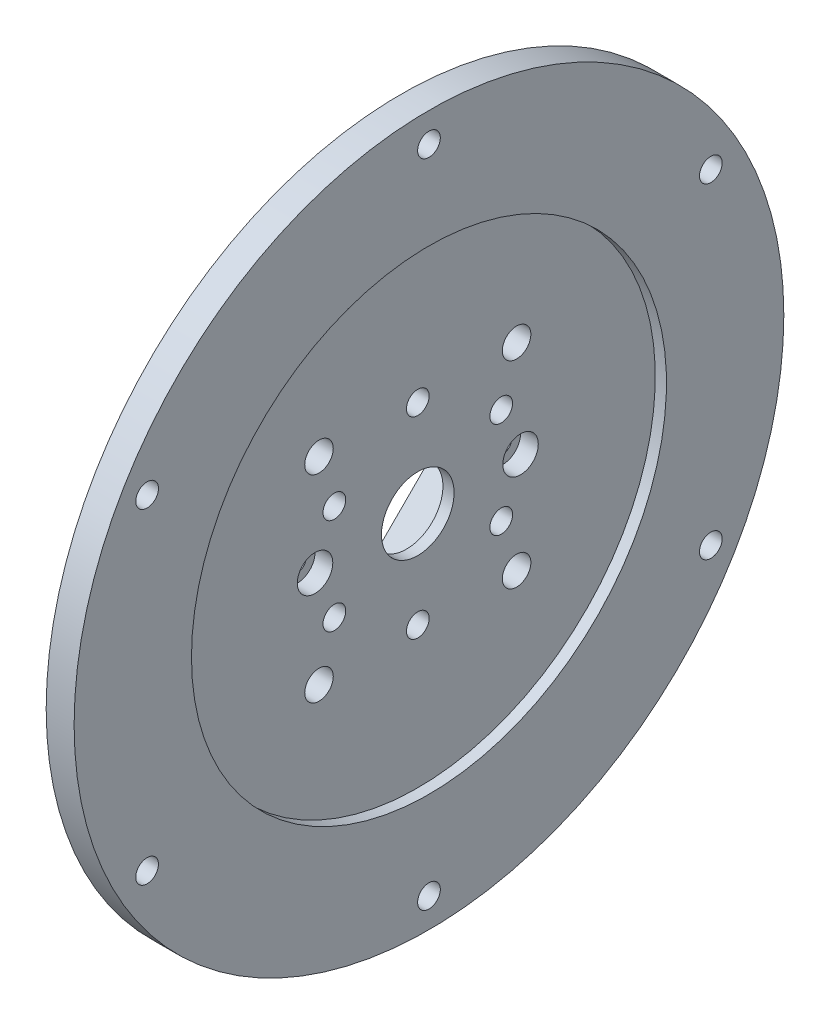
SolidWorks part; units mm, degrees
ref_plane "Front Plane" through (0, 0, 0) normal (0, 0, 1) x (1, 0, 0)
ref_plane "Top Plane" through (0, 0, 0) normal (0, 1, 0) x (1, 0, 0)
ref_plane "Right Plane" through (0, 0, 0) normal (1, 0, 0) x (0, 0, -1)
sketch "Sketch1" plane through (0, 0, 0) normal (0, 0, 1) x (1, 0, 0)
  line L0 (0, 0) -> (58.591, 0) construction
  line L2 (0, 0) -> (18.4, 0)
  line L3 (0, 0) -> (0, 2.5)
  line L4 (0, 2.5) -> (18.4, 2.5)
  line L5 (18.4, 0) -> (18.4, 2.5)
  line L6 (6, 2.5) -> (6, 6)
  line L11 (6, 6) -> (9.97, 6)
  line L16 (12.97, 6) -> (12.97, 3)
  line L17 (12.97, 3) -> (13.6304, 3)
  line L18 (13.6304, 3) -> (13.6304, 2.5)
  line L19 (13.6304, 2.5) -> (6, 2.5)
  line L22 (13.6304, 2.5) -> (16.1104, 2.5)
  line L23 (13.6304, 2.5) -> (13.6304, 4)
  line L24 (13.6304, 4) -> (16.1104, 4)
  line L25 (16.1104, 2.5) -> (16.1104, 4)
  line L27 (6, 6) -> (9.97, 6)
  line L28 (6, 6) -> (6, 9)
  line L29 (6, 9) -> (9.97, 9)
  line L30 (9.97, 6) -> (9.97, 9)
  line L31 (6, 9) -> (6, 8.25)
  line L32 (6, 8.25) -> (5, 8.25)
  line L33 (8.58, 22.001) -> (8.58, 12.476) construction
  line L34 (5, 12.476) -> (12.16, 12.476)
  line L35 (9.97, 9) -> (12.16, 9)
  line L36 (5, 7.5) -> (3, 7.5)
  line L37 (5, 8.25) -> (5, 12.476)
  line L38 (5, 7.5) -> (5, 14)
  line L39 (5, 14) -> (3, 14)
  line L40 (3, 7.5) -> (3, 14)
  line L41 (5, 22.001) -> (12.16, 22.001)
  line L42 (5, 22.001) -> (5, 30.1625)
  line L43 (5, 30.1625) -> (12.16, 30.1625)
  line L44 (12.16, 22.001) -> (12.16, 30.1625)
  line L49 (16.6304, 22.001) -> (16.6304, 7.5)
  line L51 (23.0104, 7.5) -> (23.0104, 6.5)
  line L54 (16.1104, 4) -> (13.6304, 4)
  line L56 (18.0304, 7.5) -> (23.0104, 7.5)
  line L57 (13.16, 22.001) -> (16.6304, 22.001)
  line L58 (16.1104, 3.5) -> (20.0104, 3.5)
  line L59 (29.9004, 14) -> (26.9004, 11)
  line L60 (4, 31.75) -> (18.0304, 31.75)
  line L61 (18.0304, 7.5) -> (23.0104, 7.5)
  line L62 (18.0304, 7.5) -> (18.0304, 12)
  line L63 (18.0304, 12) -> (23.0104, 12)
  line L64 (23.0104, 7.5) -> (23.0104, 12)
  line L65 (18.0304, 31.75) -> (18.0304, 12)
  line L66 (23.0104, 11) -> (26.9004, 11)
  line L67 (34.8004, 23) -> (31.3004, 19.5)
  line L68 (35.8004, 31) -> (38.7904, 33.99)
  line L69 (29.9004, 14) -> (29.9004, 15)
  line L70 (29.9004, 15) -> (22.9304, 15)
  line L71 (22.9304, 15) -> (21.0304, 15)
  line L72 (18.0304, 7.5) -> (16.6304, 7.5)
  line L73 (21.0304, 15) -> (21.0304, 43)
  line L74 (20.0304, 40) -> (10.0704, 40)
  line L75 (10.0704, 40) -> (4, 40)
  line L76 (21.0304, 43) -> (20.0304, 43)
  line L77 (22.9304, 15) -> (29.9004, 15)
  line L78 (22.9304, 15) -> (22.9304, 21)
  line L79 (22.9304, 21) -> (29.9004, 21)
  line L80 (29.9004, 15) -> (29.9004, 21)
  line L81 (10.0704, 40) -> (20.0304, 40)
  line L82 (10.0704, 40) -> (10.0704, 50)
  line L83 (10.0704, 50) -> (20.0304, 50)
  line L84 (20.0304, 40) -> (20.0304, 50)
  line L85 (4, 40) -> (4, 31.75)
  line L86 (12.97, 3) -> (12.97, 2.5)
  line L87 (31.3004, 19.5) -> (29.9004, 19.5)
  line L88 (21.51, 63.5) -> (21.51, 44)
  line L89 (21.51, 63.5) -> (25.9304, 63.5)
  line L90 (25.9304, 63.5) -> (25.9304, 25)
  line L91 (27.8304, 25) -> (25.9304, 25)
  line L92 (10.0704, 48) -> (9, 48)
  line L93 (9, 48) -> (9, 53.476)
  line L94 (9, 53.476) -> (20.0304, 53.476)
  line L95 (20.0304, 53.476) -> (20.0304, 50)
  line L96 (14.5152, 63.001) -> (14.5152, 53.476) construction
  line L97 (9, 63.001) -> (20.0304, 63.001)
  line L98 (9, 63.001) -> (9, 68.2625)
  line L99 (9, 68.2625) -> (20.0304, 68.2625)
  line L100 (20.0304, 63.001) -> (20.0304, 68.2625)
  line L101 (12.97, 6) -> (11.97, 6)
  line L102 (9, 42.5) -> (5, 42.5)
  line L103 (9, 42.5) -> (9, 55)
  line L104 (9, 55) -> (5, 55)
  line L105 (5, 42.5) -> (5, 55)
  line L106 (9.97, 6) -> (10.87, 6)
  line L107 (27.8304, 25) -> (34.8004, 25)
  line L108 (34.8004, 25) -> (34.8004, 23)
  line L109 (0, 0) -> (-2, 0)
  line L110 (0, 0) -> (0, 11)
  line L111 (27.8304, 25) -> (34.8004, 25)
  line L112 (27.8304, 25) -> (27.8304, 32.5)
  line L113 (27.8304, 32.5) -> (34.8004, 32.5)
  line L114 (34.8004, 25) -> (34.8004, 32.5)
  line L115 (35.8004, 31) -> (34.8004, 31)
  line L116 (27.8304, 32.5) -> (27.8304, 64.5)
  line L117 (21.1827, 74.025) -> (6.8477, 74.025)
  line L118 (6.8477, 74.025) -> (6.8477, 76.2)
  line L119 (38.7904, 47.29) -> (30.8304, 55.25)
  line L120 (0, 11) -> (-2, 11)
  line L121 (38.7904, 43.815) -> (30.8529, 43.815)
  line L123 (-4.8, 69.85) -> (1.55, 76.2)
  line L124 (38.7904, 47.29) -> (38.7904, 33.99)
  line L125 (-2, 0) -> (-2, 11)
  line L126 (38.7904, 37.465) -> (30.8529, 37.465)
  line L127 (30.8529, 43.815) -> (30.8529, 37.465)
  line L128 (6, 2.5) -> (6, 0)
  line L129 (0, 63.5) -> (0, 30)
  line L132 (5, 63.5) -> (0, 63.5)
  line L136 (-1.8, 30) -> (-11.76, 30)
  line L138 (-13.76, 25.4) -> (-2, 25.4)
  line L139 (-2, 25.4) -> (-2, 11.5)
  line L140 (27.8304, 64.5) -> (21.1827, 64.5)
  line L141 (-1.8, 30) -> (-11.76, 30)
  line L142 (-1.8, 30) -> (-1.8, 39)
  line L143 (-1.8, 39) -> (-11.76, 39)
  line L144 (-11.76, 30) -> (-11.76, 39)
  line L145 (21.1827, 64.5) -> (21.1827, 74.025)
  line L146 (-12.76, 37) -> (-12.76, 47.29)
  line L147 (-12.76, 37) -> (-11.76, 37)
  line L148 (30.8304, 55.25) -> (30.8304, 76.2)
  line L149 (11.97, 6) -> (11.97, 5.45)
  line L154 (-2, 11.5) -> (1, 11.5)
  line L155 (5, 60.6197) -> (24.05, 60.6197)
  line L160 (5, 60.6197) -> (5, 55.8572)
  line L161 (5, 55.8572) -> (24.05, 55.8572)
  line L166 (24.05, 60.6197) -> (24.05, 55.8572)
  line L167 (5, 60.6197) -> (24.05, 55.8572) construction
  line L172 (5, 55.8572) -> (24.05, 60.6197) construction
  line L173 (24.05, 62.2072) -> (25.9304, 62.2072)
  line L174 (11.97, 5.45) -> (10.87, 5.45)
  line L175 (10.87, 6) -> (10.87, 5.45)
  line L176 (24.05, 62.2072) -> (24.05, 54.2697)
  line L177 (24.05, 54.2697) -> (25.9304, 54.2697)
  line L178 (25.9304, 62.2072) -> (25.9304, 54.2697)
  line L179 (24.05, 62.2072) -> (25.9304, 54.2697) construction
  line L180 (24.05, 54.2697) -> (25.9304, 62.2072) construction
  line L181 (3, 19.6197) -> (15.7, 19.6197)
  line L182 (3, 19.6197) -> (3, 14.8572)
  line L183 (3, 14.8572) -> (15.7, 14.8572)
  line L184 (15.7, 19.6197) -> (15.7, 14.8572)
  line L185 (3, 19.6197) -> (15.7, 14.8572) construction
  line L186 (3, 14.8572) -> (15.7, 19.6197) construction
  line L187 (15.7, 21.2072) -> (16.6304, 21.2072)
  line L188 (15.7, 21.2072) -> (15.7, 13.2697)
  line L189 (15.7, 13.2697) -> (16.6304, 13.2697)
  line L190 (16.6304, 21.2072) -> (16.6304, 13.2697)
  line L191 (15.7, 21.2072) -> (16.6304, 13.2697) construction
  line L192 (15.7, 13.2697) -> (16.6304, 21.2072) construction
  line L193 (1, 11.5) -> (1, 6.5)
  line L194 (1, 6.5) -> (3, 6.5)
  line L195 (23.0104, 6.5) -> (20.0104, 3.5)
  line L196 (5, 63.5) -> (5, 42.5)
  line L197 (5, 42.5) -> (3, 42.5)
  line L198 (3, 42.5) -> (3, 6.5)
  line L199 (6, 0) -> (12.97, 0)
  line L200 (12.97, 0) -> (12.97, 2.5)
  line L201 (18.0304, 31.75) -> (18.0304, 35.875)
  line L202 (18.0304, 35.875) -> (21.0304, 35.875)
  line L203 (30.8304, 76.2) -> (6.8477, 76.2)
  line L204 (3.4027, 69.85) -> (7.8477, 69.85) construction
  line L205 (7.8477, 67.4687) -> (26.8977, 67.4688)
  line L206 (7.8477, 74.025) -> (7.8477, 64.5)
  line L207 (7.8477, 64.5) -> (-1.8, 64.5)
  line L208 (-1.8, 64.5) -> (-1.8, 39)
  line L209 (-12.76, 47.29) -> (-4.8, 55.25)
  line L210 (-4.8, 55.25) -> (-4.8, 69.85)
  line L211 (7.8477, 67.4687) -> (7.8477, 72.2313)
  line L212 (7.8477, 72.2313) -> (26.8977, 72.2313)
  line L213 (26.8977, 67.4688) -> (26.8977, 72.2313)
  line L214 (26.8977, 73.8187) -> (30.8304, 73.8187)
  line L215 (26.8977, 73.8187) -> (26.8977, 65.8813)
  line L216 (26.8977, 65.8813) -> (30.8304, 65.8813)
  line L217 (30.8304, 73.8187) -> (30.8304, 65.8813)
  line L218 (3.4027, 72.2313) -> (25.6277, 72.2313)
  line L219 (3.4027, 72.2313) -> (3.4027, 67.4687)
  line L220 (3.4027, 67.4687) -> (25.6277, 67.4687)
  line L221 (25.6277, 72.2313) -> (25.6277, 67.4687)
  line L222 (25.6277, 69.85) -> (21.1827, 69.85) construction
  line L223 (21.51, 44) -> (22.9304, 44)
  line L224 (22.9304, 44) -> (22.9304, 21)
  line L225 (13.6304, 4) -> (13.6304, 12.2697)
  line L226 (13.6304, 12.2697) -> (13.16, 12.2697)
  line L227 (13.16, 12.2697) -> (13.16, 22.001)
  line L228 (12.16, 9) -> (12.16, 12.476)
  line L229 (-1.8, 30) -> (0, 30)
  line L230 (9, 65.6317) -> (3.4027, 65.6317) construction
  line L231 (20.0304, 65.6317) -> (25.6277, 65.6317) construction
  line L232 (1.55, 76.2) -> (6.8477, 76.2)
  line L233 (-11.76, 30) -> (-13.76, 30)
  line L234 (-13.76, 30) -> (-13.76, 25.4)
  circle A0 centre (26.8804, 25.95) radius 0.95
  circle A1 centre (21.9804, 15.95) radius 0.95
  circle A2 centre (17.3304, 8.2) radius 0.7
  circle A3 centre (10.42, 6.45) radius 0.45
  circle A4 centre (-0.9, 30.9) radius 0.9
  point P7 (24.9902, 58.2385)
  point P131 (16.1652, 17.2385)
  point P135 (14.525, 58.2385)
  point P146 (9.35, 17.2385)
sketch "Sketch2" plane through (0, 0, 0) normal (0, 0, 1) x (1, 0, 0)
  line L0 (-1.8, 30) -> (-11.76, 30) construction
  line L1 (-2, 25.4) -> (-2, 11.5) construction
  line L3 (-13.76, 25.4) -> (-2, 25.4) construction
  line L4 (-2, 11.5) -> (1, 11.5) construction
  line L5 (1, 11.5) -> (1, 6.5) construction
  line L6 (1, 6.5) -> (3, 6.5) construction
  line L7 (3, 42.5) -> (3, 6.5) construction
  line L8 (5, 42.5) -> (3, 42.5) construction
  line L9 (5, 63.5) -> (5, 42.5) construction
  line L10 (5, 63.5) -> (0, 63.5) construction
  line L11 (0, 63.5) -> (0, 30) construction
  line L14 (-1.8, 30) -> (-11.76, 30)
  line L15 (-2, 25.4) -> (-2, 11.5)
  line L17 (-13.76, 25.4) -> (-2, 25.4)
  line L18 (-2, 11.5) -> (1, 11.5)
  line L19 (1, 11.5) -> (1, 6.5)
  line L20 (1, 6.5) -> (3, 6.5)
  line L21 (3, 42.5) -> (3, 6.5)
  line L22 (5, 42.5) -> (3, 42.5)
  line L23 (5, 63.5) -> (5, 42.5)
  line L24 (5, 63.5) -> (0, 63.5)
  line L25 (0, 63.5) -> (0, 30)
  line L28 (-1.8, 30) -> (0, 30) construction
  line L29 (-1.8, 30) -> (0, 30)
  line L30 (-13.76, 30) -> (-13.76, 25.4) construction
  line L31 (-11.76, 30) -> (-13.76, 30) construction
  line L32 (-13.76, 30) -> (-13.76, 25.4)
  line L33 (-11.76, 30) -> (-13.76, 30)
revolve "Revolve1" add sketch "Sketch2" angle 360 about L0 region at (-0.9, 29.3999, 0)
sketch "Sketch3" plane through (0, 0, 0) normal (1, 0, 0) x (0, 0, -1)
  line L0 (0, 0) -> (0, 69.85) construction
  line L1 (0, 0) -> (13.6271, 68.5079) construction
  line L2 (0, 0) -> (0, 58.2385) construction
  line L3 (0, 0) -> (50.436, 29.1192) construction
  line L4 (0, 0) -> (0, 31.75) construction
  line L5 (0, 0) -> (12.1502, 29.3332) construction
  line L6 (0, 0) -> (0, 17.2385) construction
  line L7 (0, 0) -> (14.929, 8.6192) construction
  line L8 (0, 0) -> (0, 58.2385) construction
  line L9 (0, 0) -> (50.436, 29.1192) construction
  line L10 (0, 0) -> (5.9583, 29.9542) construction
  line L11 (0, 0) -> (16.9677, 25.394) construction
  circle A0 centre (0, 0) radius 69.85 construction
  circle A1 centre (0, 0) radius 58.2385 construction
  circle A2 centre (0, 0) radius 31.75 construction
  circle A3 centre (0, 0) radius 17.2385 construction
  circle A4 centre (0, 69.85) radius 3.175
  circle A5 centre (0, 58.2385) radius 4.7625
  circle A6 centre (0, 31.75) radius 3.175
  circle A7 centre (0, 17.2385) radius 4.7625
  circle A8 centre (13.6271, 68.5079) radius 3.175
  circle A9 centre (26.7304, 64.533) radius 3.175
  circle A10 centre (38.8066, 58.0782) radius 3.175
  circle A11 centre (49.3914, 49.3914) radius 3.175
  circle A12 centre (58.0782, 38.8066) radius 3.175
  circle A13 centre (64.533, 26.7304) radius 3.175
  circle A14 centre (68.5079, 13.6271) radius 3.175
  circle A15 centre (69.85, 0) radius 3.175
  circle A16 centre (68.5079, -13.6271) radius 3.175
  circle A17 centre (64.533, -26.7304) radius 3.175
  circle A18 centre (58.0782, -38.8066) radius 3.175
  circle A19 centre (49.3914, -49.3914) radius 3.175
  circle A20 centre (38.8066, -58.0782) radius 3.175
  circle A21 centre (26.7304, -64.533) radius 3.175
  circle A22 centre (13.6271, -68.5079) radius 3.175
  circle A23 centre (0, -69.85) radius 3.175
  circle A24 centre (-13.6271, -68.5079) radius 3.175
  circle A25 centre (-26.7304, -64.533) radius 3.175
  circle A26 centre (-38.8066, -58.0782) radius 3.175
  circle A27 centre (-49.3914, -49.3914) radius 3.175
  circle A28 centre (-58.0782, -38.8066) radius 3.175
  circle A29 centre (-64.533, -26.7304) radius 3.175
  circle A30 centre (-68.5079, -13.6271) radius 3.175
  circle A31 centre (-69.85, 0) radius 3.175
  circle A32 centre (-68.5079, 13.6271) radius 3.175
  circle A33 centre (-64.533, 26.7304) radius 3.175
  circle A34 centre (-58.0782, 38.8066) radius 3.175
  circle A35 centre (-49.3914, 49.3914) radius 3.175
  circle A36 centre (-38.8066, 58.0782) radius 3.175
  circle A37 centre (-26.7304, 64.533) radius 3.175
  circle A38 centre (-13.6271, 68.5079) radius 3.175
  circle A47 centre (50.436, 29.1192) radius 4.7625
  circle A48 centre (50.436, -29.1192) radius 4.7625
  circle A49 centre (0, -58.2385) radius 4.7625
  circle A50 centre (-50.436, -29.1192) radius 4.7625
  circle A51 centre (-50.436, 29.1192) radius 4.7625
  circle A58 centre (12.1502, 29.3332) radius 3.175
  circle A59 centre (22.4506, 22.4506) radius 3.175
  circle A60 centre (29.3332, 12.1502) radius 3.175
  circle A61 centre (31.75, 0) radius 3.175
  circle A62 centre (29.3332, -12.1502) radius 3.175
  circle A63 centre (22.4506, -22.4506) radius 3.175
  circle A64 centre (12.1502, -29.3332) radius 3.175
  circle A65 centre (0, -31.75) radius 3.175
  circle A66 centre (-12.1502, -29.3332) radius 3.175
  circle A67 centre (-22.4506, -22.4506) radius 3.175
  circle A68 centre (-29.3332, -12.1502) radius 3.175
  circle A69 centre (-31.75, 0) radius 3.175
  circle A70 centre (-29.3332, 12.1502) radius 3.175
  circle A71 centre (-22.4506, 22.4506) radius 3.175
  circle A72 centre (14.929, 8.6192) radius 4.7625
  circle A73 centre (14.929, -8.6192) radius 4.7625
  circle A74 centre (0, -17.2385) radius 4.7625
  circle A75 centre (-14.929, -8.6192) radius 4.7625
  circle A76 centre (-14.929, 8.6192) radius 4.7625
  circle A77 centre (0, 0) radius 50
  circle A78 centre (0, 0) radius 9
  circle A79 centre (-12.1502, 29.3332) radius 3.175
  circle A80 centre (0, 0) radius 76.2
  circle A81 centre (0, 0) radius 74.025
  circle A82 centre (0, 69.85) radius 3.9687
  circle A83 centre (49.3914, 49.3914) radius 3.9687
  circle A84 centre (69.85, 0) radius 3.9688
  circle A85 centre (49.3914, -49.3914) radius 3.9687
  circle A86 centre (0, -69.85) radius 3.9687
  circle A87 centre (-49.3914, -49.3914) radius 3.9687
  circle A88 centre (-69.85, 0) radius 3.9688
  circle A89 centre (-49.3914, 49.3914) radius 3.9687
  circle A90 centre (0, 69.85) radius 2.3812
  circle A91 centre (13.6271, 68.5079) radius 2.3812
  circle A92 centre (26.7304, 64.533) radius 2.3813
  circle A93 centre (38.8066, 58.0782) radius 2.3812
  circle A94 centre (49.3914, 49.3914) radius 2.3812
  circle A95 centre (58.0782, 38.8066) radius 2.3812
  circle A96 centre (64.533, 26.7304) radius 2.3813
  circle A97 centre (68.5079, 13.6271) radius 2.3813
  circle A98 centre (69.85, 0) radius 2.3813
  circle A99 centre (68.5079, -13.6271) radius 2.3813
  circle A100 centre (64.533, -26.7304) radius 2.3813
  circle A101 centre (58.0782, -38.8066) radius 2.3812
  circle A102 centre (49.3914, -49.3914) radius 2.3812
  circle A103 centre (38.8066, -58.0782) radius 2.3812
  circle A104 centre (26.7304, -64.533) radius 2.3813
  circle A105 centre (13.6271, -68.5079) radius 2.3812
  circle A106 centre (0, -69.85) radius 2.3812
  circle A107 centre (-13.6271, -68.5079) radius 2.3812
  circle A108 centre (-26.7304, -64.533) radius 2.3813
  circle A109 centre (-38.8066, -58.0782) radius 2.3812
  circle A110 centre (-49.3914, -49.3914) radius 2.3812
  circle A111 centre (-58.0782, -38.8066) radius 2.3812
  circle A112 centre (-64.533, -26.7304) radius 2.3812
  arc A113 (3.0399, 30.8338) -> (8.9911, 29.65) centre (5.9583, 29.9542) cw
  arc A114 (14.6081, 27.3234) -> (19.6532, 23.9523) centre (16.9677, 25.394) cw
  arc A115 (23.9523, 19.6532) -> (27.3234, 14.6081) centre (25.394, 16.9677) cw
  arc A116 (29.65, 8.9911) -> (30.8338, 3.0399) centre (29.9542, 5.9583) cw
  arc A117 (30.8338, -3.0399) -> (29.65, -8.9911) centre (29.9542, -5.9583) cw
  arc A118 (27.3234, -14.6081) -> (23.9523, -19.6532) centre (25.394, -16.9677) cw
  arc A119 (19.6532, -23.9523) -> (14.6081, -27.3234) centre (16.9677, -25.394) cw
  arc A120 (8.9911, -29.65) -> (3.0399, -30.8338) centre (5.9583, -29.9542) cw
  arc A121 (-3.0399, -30.8338) -> (-8.9911, -29.65) centre (-5.9583, -29.9542) cw
  arc A122 (-14.6081, -27.3234) -> (-19.6532, -23.9523) centre (-16.9677, -25.394) cw
  arc A123 (-23.9523, -19.6532) -> (-27.3234, -14.6081) centre (-25.394, -16.9677) cw
  arc A124 (-29.65, -8.9911) -> (-30.8338, -3.0399) centre (-29.9542, -5.9583) cw
  arc A125 (-30.8338, 3.0399) -> (-29.65, 8.9911) centre (-29.9542, 5.9583) cw
  arc A126 (-27.3234, 14.6081) -> (-23.9523, 19.6532) centre (-25.394, 16.9677) cw
  arc A127 (-19.6532, 23.9523) -> (-14.6081, 27.3234) centre (-16.9677, 25.394) cw
  arc A128 (-8.9911, 29.65) -> (-3.0399, 30.8338) centre (-5.9583, 29.9542) cw
  arc A129 (26.9875, 0) -> (26.9932, 0.1932) centre (30.2705, 0) cw
  arc A130 (65.0988, 0.2771) -> (65.0875, 0) centre (68.4964, 0) ccw
  circle A131 centre (1.5875, 0) radius 40
  circle A132 centre (1.5875, 0) radius 2.5
  circle A133 centre (1.5875, 0) radius 3
  circle A134 centre (1.5875, 0) radius 43
  circle A135 centre (-68.5079, -13.6271) radius 2.3813
  circle A136 centre (-69.85, 0) radius 2.3813
  circle A137 centre (-68.5079, 13.6271) radius 2.3813
  circle A138 centre (-64.533, 26.7304) radius 2.3812
  circle A139 centre (-58.0782, 38.8066) radius 2.3812
  circle A140 centre (-49.3914, 49.3914) radius 2.3812
  circle A141 centre (-38.8066, 58.0782) radius 2.3812
  circle A142 centre (-26.7304, 64.533) radius 2.3813
  circle A143 centre (-13.6271, 68.5079) radius 2.3812
  circle A144 centre (0, 58.2385) radius 2.3812
  circle A145 centre (0, 58.2385) radius 3.9688
  circle A146 centre (50.436, 29.1192) radius 3.9688
  circle A147 centre (50.436, 29.1192) radius 2.3813
  circle A148 centre (50.436, -29.1192) radius 3.9687
  circle A149 centre (50.436, -29.1192) radius 2.3812
  circle A150 centre (0, -58.2385) radius 3.9687
  circle A151 centre (0, -58.2385) radius 2.3812
  circle A152 centre (-50.436, -29.1192) radius 3.9687
  circle A153 centre (-50.436, -29.1192) radius 2.3812
  circle A154 centre (-50.436, 29.1192) radius 3.9687
  circle A155 centre (-50.436, 29.1192) radius 2.3812
  spline S1 degree 4 number of poles 499 (26.9875, 0) -> (26.9932, 0.1932)
  spline S3 degree 4 number of poles 617 (65.0875, 0) -> (65.0988, 0.2771)
  point P116 (0, 0)
  point P225 (0, 0)
sketch "Sketch4" plane through (0, 0, 0) normal (1, 0, 0) x (0, 0, -1)
  circle A0 centre (-14.929, -8.6192) radius 4.7625 construction
  circle A1 centre (-14.929, 8.6192) radius 4.7625 construction
  circle A2 centre (0, 17.2385) radius 4.7625 construction
  circle A3 centre (14.929, 8.6192) radius 4.7625 construction
  circle A4 centre (14.929, -8.6192) radius 4.7625 construction
  circle A5 centre (0, -17.2385) radius 4.7625 construction
  circle A6 centre (0, -58.2385) radius 4.7625 construction
  circle A7 centre (-50.436, -29.1192) radius 4.7625 construction
  circle A8 centre (50.436, -29.1192) radius 4.7625 construction
  circle A9 centre (50.436, 29.1192) radius 4.7625 construction
  circle A10 centre (0, 58.2385) radius 4.7625 construction
  circle A11 centre (-50.436, 29.1192) radius 4.7625 construction
  circle A12 centre (-14.929, -8.6192) radius 4.7625
  circle A13 centre (-14.929, 8.6192) radius 4.7625
  circle A14 centre (0, 17.2385) radius 4.7625
  circle A15 centre (14.929, 8.6192) radius 4.7625
  circle A16 centre (14.929, -8.6192) radius 4.7625
  circle A17 centre (0, -17.2385) radius 4.7625
  circle A18 centre (0, -58.2385) radius 4.7625
  circle A19 centre (-50.436, -29.1192) radius 4.7625
  circle A20 centre (50.436, -29.1192) radius 4.7625
  circle A21 centre (50.436, 29.1192) radius 4.7625
  circle A22 centre (0, 58.2385) radius 4.7625
  circle A23 centre (-50.436, 29.1192) radius 4.7625
  circle A24 centre (0, 58.2385) radius 2.032
  circle A25 centre (50.436, 29.1192) radius 2.032
  circle A26 centre (50.436, -29.1192) radius 2.032
  circle A27 centre (0, -58.2385) radius 2.032
  circle A28 centre (-50.436, -29.1192) radius 2.032
  circle A29 centre (-50.436, 29.1192) radius 2.032
  circle A30 centre (-14.929, 8.6192) radius 2.032
  circle A31 centre (0, 17.2385) radius 2.032
  circle A32 centre (14.929, 8.6192) radius 2.032
  circle A33 centre (14.929, -8.6192) radius 2.032
  circle A34 centre (0, -17.2385) radius 2.032
  circle A35 centre (-14.929, -8.6192) radius 2.032
  dimension "D1" = 4.064
extrude "Cut-Extrude1" cut sketch "Sketch4" against normal through all and the other way through all contours A29 | A30 | A31 | A32 | A33 | A34 | A35 | A25 | A26 | A24 | A28 | A27
sketch "Sketch5" plane through (3, 0, 0) normal (1, 0, 0) x (0, 0, -1)
  line L0 (-18.385, 0) -> (0, 0) construction
  line L1 (0, 0) -> (18.385, 0) construction
  circle A0 centre (-18.385, 0) radius 1.5875
  circle A1 centre (18.385, 0) radius 1.5875
  dimension "D2" = 3.175
  dimension "D1" = 36.77
extrude "Cut-Extrude2" cut sketch "Sketch5" against normal through all
sketch "Sketch6" plane through (3, 0, 0) normal (1, 0, 0) x (0, 0, -1)
  circle A0 centre (-18.385, 0) radius 3.175
  circle A1 centre (18.385, 0) radius 3.175
  dimension "D1" = 6.35
extrude "Cut-Extrude3" cut sketch "Sketch6" against normal blind 3.175
sketch "Sketch7" plane through (-13.76, 0, 0) normal (-1, 0, 0) x (0, 0, 1)
  line L0 (3.0706, 25.2137) -> (25.2137, 3.0706)
  line L1 (25.2137, -3.0706) -> (3.0706, -25.2137)
  line L2 (-3.0706, -25.2137) -> (-25.2137, -3.0706)
  line L3 (-25.2137, 3.0706) -> (-3.0706, 25.2137)
  circle A3 centre (0, 0) radius 25.4 construction
  circle A4 centre (0, 0) radius 25.4
  point P15 (0, 0)
  circle M5 centre (0, 0) radius 25.4
  dimension "D2" = 40
  dimension "D1" = 4
extrude "Boss-Extrude1" add sketch "Sketch7" against normal up to next contours L0 M5 | L3 M5 | L2 M5 | L1 M5 region at (-13.76, 15.6843, 15.6843) region at (-13.76, 15.6843, -15.6843) region at (-13.76, -15.6843, 15.6843) region at (-13.76, -15.6843, -15.6843)
fillet "Fillet1" radius 3.175 8 edges at (-7.88, -25.2137, -3.0706) (-7.88, -25.2137, 3.0706) (-7.88, -3.0706, 25.2137) (-7.88, 3.0706, 25.2137) (-7.88, -3.0706, -25.2137) (-7.88, 3.0706, -25.2137) (-7.88, 25.2137, 3.0706) (-7.88, 25.2137, -3.0706)
sketch "Sketch8" plane through (-13.76, 0, 0) normal (-1, 0, 0) x (0, 0, 1)
  line L0 (0, 0) -> (17.6777, 17.6777) construction
  line L1 (0, 0) -> (13.9248, 0) construction
  line L2 (17.6777, 17.6777) -> (21.2132, 21.2132) construction
  line L3 (17.6777, 17.6777) -> (14.1421, 14.1421) construction
  line L7 (3.874, 24.4103) -> (24.4103, 3.874) construction
  circle A0 centre (17.6777, 17.6777) radius 2.5527
  circle A1 centre (0, 0) radius 30 construction
  circle A2 centre (17.6777, -17.6777) radius 2.5527
  circle A3 centre (-17.6777, -17.6777) radius 2.5527
  circle A4 centre (-17.6777, 17.6777) radius 2.5527
  point P20 (0, 0)
  dimension "D2" = 5.1054
  dimension "D1" = 45
  dimension "D3" = 4
extrude "Cut-Extrude4" cut sketch "Sketch8" against normal through all
